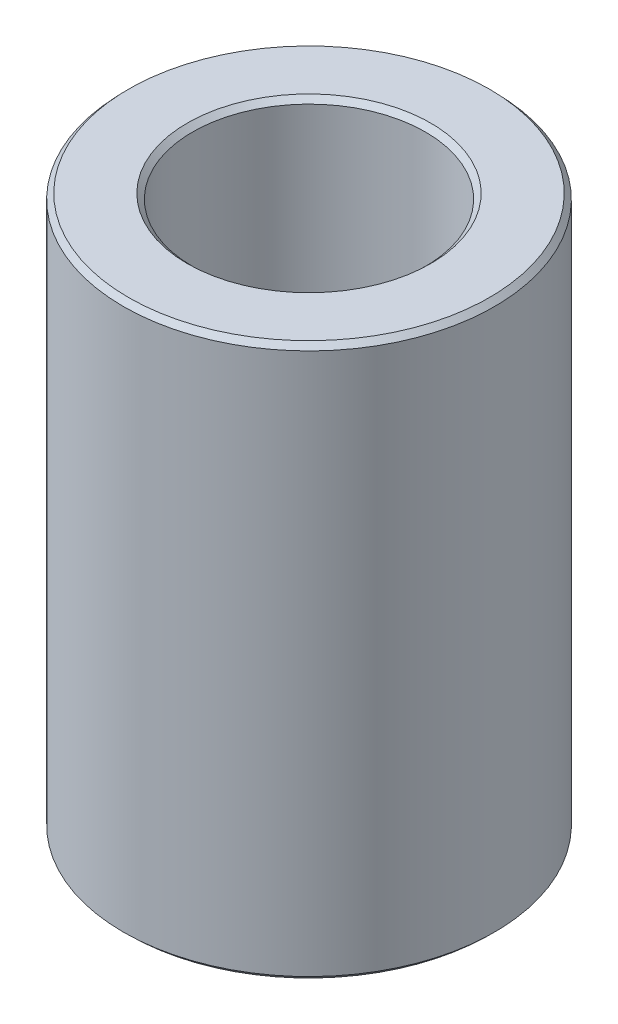
SolidWorks part; units mm, degrees
ref_plane "Front Plane" through (0, 0, 0) normal (0, 0, 1) x (1, 0, 0)
ref_plane "Top Plane" through (0, 0, 0) normal (0, 1, 0) x (1, 0, 0)
ref_plane "Right Plane" through (0, 0, 0) normal (1, 0, 0) x (0, 0, -1)
sketch "Sketch1" plane through (0, 0, 0) normal (0, 1, 0) x (1, 0, 0)
  circle A0 centre (0, 0) radius 35
  dimension "SLEEVE_OD" = 70
extrude "Boss-Extrude1" add sketch "Sketch1" along normal blind 104.166
sketch "Sketch2" plane through (0, 0, 0) normal (0, 1, 0) x (1, 0, 0)
  circle A0 centre (0, 0) radius 21.9673
  dimension "BORE_D" = 43.9346
extrude "Cut-Extrude1" cut sketch "Sketch2" along normal through all
chamfer "Chamfer1" distance 1.0018 angle 43.55 4 edges at (0, 104.166, 21.9673) (0, 0, 21.9673) (0, 0, 35) (0, 104.166, 35) first distance on face at (0, 104.166, 21.9673) first distance on face at (0, 0, 21.9673) first distance on face at (0, 104.166, 35)
